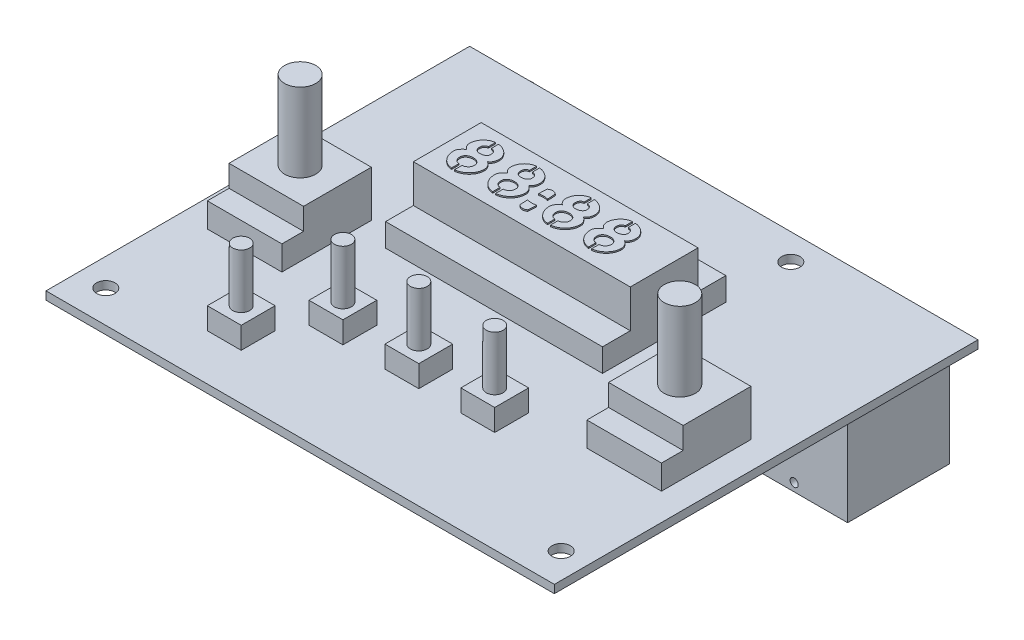
SolidWorks part; units mm, degrees
ref_plane "Front Plane" through (0, 0, 0) normal (0, 0, 1) x (1, 0, 0)
ref_plane "Top Plane" through (0, 0, 0) normal (0, 1, 0) x (1, 0, 0)
ref_plane "Right Plane" through (0, 0, 0) normal (1, 0, 0) x (0, 0, -1)
sketch "Sketch1" plane through (0, 0, 0) normal (0, 1, 0) x (1, 0, 0)
  line L1 (-47.625, 39.6875) -> (47.625, 39.6875)
  line L2 (-47.625, 39.6875) -> (-47.625, -39.6875)
  line L3 (-47.625, -39.6875) -> (47.625, -39.6875)
  line L4 (47.625, 39.6875) -> (47.625, -39.6875)
  line L5 (-47.625, 39.6875) -> (47.625, -39.6875) construction
  line L6 (-47.625, -39.6875) -> (47.625, 39.6875) construction
  point P0 (0, 0)
  dimension "D1" = 95.25
  dimension "D2" = 79.375
extrude "Boss-Extrude1" add sketch "Sketch1" along normal blind 1.524
hole_wizard "#29 (0.136) Diameter Hole1" positions "Sketch2" profile "Sketch3" hole size "#29" standard "ANSI Inch" end condition through all
sketch "Sketch2" plane through (0, 1.524, 0) normal (0, 1, 0) x (1, 0, 0)
  line L0 (47.625, -39.6875) -> (47.625, 39.6875) construction
  line L1 (-47.625, -39.6875) -> (47.625, -39.6875) construction
  line L2 (-47.625, 39.6875) -> (-47.625, -39.6875) construction
  line L3 (47.625, 39.6875) -> (-47.625, 39.6875) construction
  point P0 (42.8498, -33.6423)
  point P2 (17.4498, 34.7853)
  point P4 (-25.8318, 22.2123)
  point P6 (-42.4688, -33.6423)
  dimension "D1" = 4.7752
  dimension "D2" = 6.0452
  dimension "D3" = 6.0452
  dimension "D4" = 5.1562
  dimension "D5" = 30.1752
  dimension "D6" = 4.9022
  dimension "D7" = 17.4752
  dimension "D8" = 21.7932
sketch "Sketch3" plane through (42.8498, 1.524, 33.6423) normal (1, 0, 0) x (0, 0, 1)
  line L0 (0, 0) -> (0, 1.524)
  line L1 (0, 1.524) -> (1.7272, 1.524)
  line L2 (1.7272, 1.524) -> (1.7272, 0)
  line L5 (1.7272, 0) -> (0, 0)
  line L11 (0, -6.35) -> (0, 107.95) construction
  dimension "Thru Hole Dia." = 3.4544
  dimension "Thru Hole Depth" = 1.524
sketch "Sketch4" plane through (0, 1.524, 0) normal (0, 1, 0) x (1, 0, 0)
  line L0 (47.625, -39.6875) -> (47.625, 39.6875) construction
  line L1 (28.575, 2.2225) -> (42.545, 2.2225)
  line L2 (28.575, 2.2225) -> (28.575, -14.5415)
  line L3 (28.575, -14.5415) -> (42.545, -14.5415)
  line L4 (42.545, 2.2225) -> (42.545, -14.5415)
  line L5 (28.575, 2.2225) -> (42.545, -14.5415) construction
  line L6 (28.575, -14.5415) -> (42.545, 2.2225) construction
  line L7 (-47.625, -39.6875) -> (47.625, -39.6875) construction
  line L9 (-28.575, 2.2225) -> (-42.545, 2.2225)
  line L10 (-28.575, 2.2225) -> (-28.575, -14.5415)
  line L11 (-28.575, -14.5415) -> (-42.545, -14.5415)
  line L12 (-42.545, 2.2225) -> (-42.545, -14.5415)
  line L13 (-28.575, 2.2225) -> (-42.545, -14.5415) construction
  line L14 (-28.575, -14.5415) -> (-42.545, 2.2225) construction
  line L15 (-47.625, 39.6875) -> (-47.625, -39.6875) construction
  point P0 (35.56, -6.1595)
  point P9 (-35.56, -6.1595)
  dimension "D1" = 16.764
  dimension "D2" = 13.97
  dimension "D3" = 19.05
  dimension "D4" = 41.91
  dimension "D5" = 41.91
  dimension "D6" = 19.05
extrude "Boss-Extrude2" add sketch "Sketch4" along normal blind 4.572
sketch "Sketch5" plane through (0, 6.096, 0) normal (0, 1, 0) x (1, 0, 0)
  line L0 (-28.575, -14.5415) -> (-28.575, 2.2225) construction
  line L1 (-42.545, 2.2225) -> (-28.575, 2.2225)
  line L2 (-42.545, 2.2225) -> (-42.545, -10.4775)
  line L3 (-42.545, -10.4775) -> (-28.575, -10.4775)
  line L4 (-28.575, 2.2225) -> (-28.575, -10.4775)
  line L5 (42.545, -14.5415) -> (42.545, 2.2225) construction
  line L6 (28.575, 2.2225) -> (42.545, 2.2225)
  line L7 (28.575, 2.2225) -> (28.575, -10.4775)
  line L8 (28.575, -10.4775) -> (42.545, -10.4775)
  line L9 (42.545, 2.2225) -> (42.545, -10.4775)
  line L10 (0, 39.6875) -> (0, -39.6875) construction
  line L11 (47.625, 39.6875) -> (-47.625, 39.6875) construction
  line L12 (-47.625, -39.6875) -> (47.625, -39.6875) construction
  line L33 (-42.545, 2.2225) -> (-42.545, -14.5415) construction
  dimension "D1" = 12.7
extrude "Boss-Extrude3" add sketch "Sketch5" along normal blind 4.064
sketch "Sketch8" plane through (0, 1.524, 0) normal (0, 1, 0) x (1, 0, 0)
  line L0 (0, 39.6875) -> (0, -39.6875) construction
  line L1 (47.625, 39.6875) -> (-47.625, 39.6875) construction
  line L2 (-47.625, -39.6875) -> (47.625, -39.6875) construction
  line L3 (-47.625, 39.6875) -> (-47.625, -39.6875) construction
  line L5 (-26.035, -31.0515) -> (-19.685, -31.0515)
  line L6 (-26.035, -31.0515) -> (-26.035, -24.7015)
  line L7 (-26.035, -24.7015) -> (-19.685, -24.7015)
  line L8 (-3.175, -14.2875) -> (3.175, -20.6375) construction
  line L9 (-3.175, -20.6375) -> (3.175, -14.2875) construction
  line L10 (17.399, -14.2875) -> (17.399, -20.6375)
  line L11 (11.049, -14.2875) -> (17.399, -14.2875)
  line L12 (11.049, -14.2875) -> (11.049, -20.6375)
  line L13 (11.049, -20.6375) -> (17.399, -20.6375)
  line L14 (3.175, -14.2875) -> (3.175, -20.6375)
  line L15 (-3.175, -14.2875) -> (3.175, -14.2875)
  line L16 (-3.175, -14.2875) -> (-3.175, -20.6375)
  line L17 (-3.175, -20.6375) -> (3.175, -20.6375)
  line L18 (-11.049, -14.2875) -> (-11.049, -20.6375)
  line L19 (-17.399, -14.2875) -> (-11.049, -14.2875)
  line L20 (-17.399, -14.2875) -> (-17.399, -20.6375)
  line L21 (-17.399, -20.6375) -> (-11.049, -20.6375)
  line L22 (-19.685, -31.0515) -> (-19.685, -24.7015)
  line L23 (-26.035, -31.0515) -> (-19.685, -24.7015) construction
  line L24 (-26.035, -24.7015) -> (-19.685, -31.0515) construction
  point P6 (0, -17.4625)
  point P13 (-22.86, -27.8765)
  dimension "D1" = 30.226
  dimension "D2" = 58.674
  dimension "D3" = 6.35
  dimension "D4" = 53.975
  dimension "D5" = 27.94
  dimension "D6" = 14.986
extrude "Boss-Extrude5" add sketch "Sketch8" along normal blind 4.064
sketch "Sketch9" plane through (0, 5.588, 0) normal (0, 1, 0) x (1, 0, 0)
  line L0 (-17.399, -14.2875) -> (-11.049, -20.6375) construction
  line L1 (-3.175, -14.2875) -> (3.175, -20.6375) construction
  line L2 (11.049, -14.2875) -> (17.399, -20.6375) construction
  line L3 (-26.035, -24.7015) -> (-19.685, -31.0515) construction
  circle A0 centre (-13.9422, -17.7443) radius 1.5875
  circle A1 centre (0, -17.4625) radius 1.5875
  circle A2 centre (14.224, -17.4625) radius 1.5875
  circle A3 centre (-22.86, -27.8765) radius 1.5875
  dimension "D1" = 3.175
extrude "Boss-Extrude6" add sketch "Sketch9" along normal blind 10.16
sketch "Sketch10" plane through (0, 10.16, 0) normal (0, 1, 0) x (1, 0, 0)
  line L0 (-42.545, 2.2225) -> (-28.575, -10.4775) construction
  line L1 (28.575, 2.2225) -> (42.545, -10.4775) construction
  circle A0 centre (-35.56, -4.1275) radius 2.921
  circle A1 centre (35.56, -4.1275) radius 2.921
  dimension "D1" = 5.842
extrude "Boss-Extrude7" add sketch "Sketch10" along normal blind 14.732
sketch "Sketch11" plane through (0, 0, -39.6875) normal (0, 0, -1) x (-1, 0, 0)
  line L0 (-47.625, 0) -> (47.625, 0) construction
  line L1 (-42.2402, 0) -> (-22.225, 0)
  line L2 (-42.2402, 0) -> (-42.2402, -21.336)
  line L3 (-42.2402, -21.336) -> (-22.225, -21.336)
  line L4 (-22.225, 0) -> (-22.225, -21.336)
  line L5 (-47.625, 1.524) -> (-47.625, 0) construction
  dimension "D1" = 25.4
  dimension "D2" = 20.0152
  dimension "D3" = 21.336
extrude "Boss-Extrude8" add sketch "Sketch11" against normal blind 19.05 separate body
sketch "Sketch12" plane through (0, 0, -39.6875) normal (0, 0, -1) x (-1, 0, 0)
  line L0 (-32.2326, 0) -> (-32.2326, -21.336) construction
  line L1 (-22.225, 0) -> (-42.2402, 0) construction
  line L2 (-42.2402, -21.336) -> (-22.225, -21.336) construction
  circle A0 centre (-32.2326, -10.541) radius 6.985
  dimension "D1" = 13.97
  dimension "D2" = 10.795
extrude "Cut-Extrude1" cut sketch "Sketch12" against normal blind 3.175
hole_wizard "#53 (0.0595) Diameter Hole1" positions "Sketch13" profile "Sketch14" hole size "#53" standard "ANSI Inch" end condition through all
sketch "Sketch13" plane through (0, 0, -39.6875) normal (0, 0, -1) x (-1, 0, 0)
  line L1 (-32.2326, -10.541) -> (-32.2326, -21.336) construction
  line L2 (-42.2402, -21.336) -> (-22.225, -21.336) construction
  line L3 (-23.4886, -5.4927) -> (-32.2326, -10.541) construction
  line L5 (-40.9765, -5.4927) -> (-32.2326, -10.541) construction
  line L7 (-22.225, -21.336) -> (-22.225, 0) construction
  line L8 (-42.2402, 0) -> (-42.2402, -21.336) construction
  point P0 (-40.9765, -5.4927)
  point P2 (-23.4886, -5.4927)
  point P14 (-32.2326, -19.8183)
  dimension "D1" = 1.5176
  dimension "D2" = 120
  dimension "D3" = 120
  dimension "D4" = 1.2637
  dimension "D5" = 1.2637
sketch "Sketch14" plane through (40.9765, -5.4927, -39.6875) normal (1, 0, 0) x (0, 1, 0)
  line L0 (0, 0) -> (0, 79.375)
  line L1 (0, 79.375) -> (0.7556, 79.375)
  line L2 (0.7556, 79.375) -> (0.7556, 0)
  line L5 (0.7556, 0) -> (0, 0)
  line L11 (0, -6.35) -> (0, 107.95) construction
  dimension "Thru Hole Dia." = 1.5113
  dimension "Thru Hole Depth" = 79.375
sketch "Sketch15" plane through (0, 0, -39.6875) normal (0, 0, -1) x (-1, 0, 0)
  line L0 (-47.625, 0) -> (47.625, 0) construction
  line L1 (34.925, 0) -> (40.894, 0)
  line L2 (34.925, 0) -> (34.925, -5.334)
  line L3 (34.925, -5.334) -> (40.894, -5.334)
  line L4 (40.894, 0) -> (40.894, -5.334)
  line L5 (47.625, 1.524) -> (47.625, 0) construction
  dimension "D1" = 5.969
  dimension "D2" = 5.334
  dimension "D3" = 12.7
extrude "Boss-Extrude9" add sketch "Sketch15" against normal blind 13.97
sketch "Sketch16" plane through (0, 0, -39.6875) normal (0, 0, -1) x (-1, 0, 0)
  line L0 (34.925, 0) -> (40.894, -5.334) construction
  circle A0 centre (37.9095, -2.667) radius 1.778
  circle A1 centre (37.9095, -2.667) radius 2.54
  dimension "D1" = 5.08
  dimension "D2" = 3.556
extrude "Boss-Extrude10" add sketch "Sketch16" along normal blind 2.032 draft 9
sketch "Sketch17" plane through (0, 0, -39.6875) normal (0, 0, -1) x (-1, 0, 0)
  circle A0 centre (37.9095, -2.667) radius 1.778
extrude "Cut-Extrude2" cut sketch "Sketch17" against normal blind 12.7
sketch "Sketch18" plane through (0, 1.524, 0) normal (0, 1, 0) x (1, 0, 0)
  line L0 (-47.625, 39.6875) -> (-47.625, -39.6875) construction
  line L1 (-22.733, -0.9525) -> (17.907, -0.9525)
  line L2 (-22.733, -0.9525) -> (-22.733, 22.1615)
  line L3 (-22.733, 22.1615) -> (17.907, 22.1615)
  line L4 (17.907, -0.9525) -> (17.907, 22.1615)
  line L5 (47.625, 39.6875) -> (-47.625, 39.6875) construction
  dimension "D1" = 40.64
  dimension "D2" = 23.114
  dimension "D3" = 65.532
  dimension "D4" = 40.64
extrude "Boss-Extrude11" add sketch "Sketch18" along normal blind 4.318
sketch "Sketch19" plane through (0, 5.842, 0) normal (0, 1, 0) x (1, 0, 0)
  line L0 (-22.733, 22.1615) -> (17.907, -0.9525) construction
  line L1 (17.907, -0.9525) -> (17.907, 22.1615) construction
  line L2 (-22.733, 4.2545) -> (17.907, 4.2545)
  line L3 (-22.733, 4.2545) -> (-22.733, 16.9545)
  line L4 (-22.733, 16.9545) -> (17.907, 16.9545)
  line L5 (17.907, 4.2545) -> (17.907, 16.9545)
  line L6 (-22.733, 4.2545) -> (17.907, 16.9545) construction
  line L7 (-22.733, 16.9545) -> (17.907, 4.2545) construction
  point P4 (-2.413, 10.6045)
  dimension "D1" = 12.7
extrude "Boss-Extrude12" add sketch "Sketch19" along normal blind 7.112
sketch "Sketch20" plane through (0, 0, 0) normal (0, -1, 0) x (1, 0, 0)
  line L0 (-47.625, 39.6875) -> (47.625, 39.6875) construction
  line L1 (17.653, 35.8775) -> (-15.367, 35.8775)
  line L2 (17.653, 35.8775) -> (17.653, 33.4675)
  line L3 (17.653, 33.4675) -> (-15.367, 33.4675)
  line L4 (-15.367, 35.8775) -> (-15.367, 33.4675)
  line L5 (47.625, 39.6875) -> (47.625, -39.6875) construction
  dimension "D1" = 33.02
  dimension "D2" = 2.41
  dimension "D3" = 3.81
  dimension "D4" = 29.972
extrude "Boss-Extrude13" add sketch "Sketch20" along normal blind 2.54
sketch "Sketch21" plane through (0, 0, 0) normal (0, -1, 0) x (1, 0, 0)
  line L0 (47.625, -39.6875) -> (-34.925, -39.6875) construction
  line L1 (3.429, -39.6875) -> (-5.461, -39.6875)
  line L2 (3.429, -39.6875) -> (3.429, -35.1155)
  line L3 (3.429, -35.1155) -> (-5.461, -35.1155)
  line L4 (-5.461, -39.6875) -> (-5.461, -35.1155)
  line L5 (47.625, 39.6875) -> (47.625, -39.6875) construction
  dimension "D1" = 8.89
  dimension "D2" = 4.572
  dimension "D3" = 53.086
extrude "Boss-Extrude14" add sketch "Sketch21" along normal blind 4.826
sketch "Sketch22" plane through (0, 0, -39.6875) normal (0, 0, -1) x (-1, 0, 0)
  line L0 (-3.429, 0) -> (5.461, -4.826) construction
  line L1 (5.461, -4.826) -> (5.461, 0) construction
  line L2 (-3.429, -3.429) -> (5.461, -3.429)
  line L3 (-3.429, -3.429) -> (-3.429, -1.397)
  line L4 (-3.429, -1.397) -> (5.461, -1.397)
  line L5 (5.461, -3.429) -> (5.461, -1.397)
  line L6 (-3.429, -3.429) -> (5.461, -1.397) construction
  line L7 (-3.429, -1.397) -> (5.461, -3.429) construction
  point P4 (1.016, -2.413)
  dimension "D1" = 2.032
extrude "Boss-Extrude15" add sketch "Sketch22" along normal blind 1.524
sketch "Sketch23" plane through (0, 12.954, 0) normal (0, 1, 0) x (1, 0, 0)
  line L0 (17.907, 4.2545) -> (17.907, 16.9545) construction
  line L1 (17.907, 16.9545) -> (-22.733, 16.9545) construction
  text T0 "88:88" font "Stencilia-Bold" height in points 25
  dimension "D1" = 39.3082
  dimension "D2" = 10.3887
extrude "Boss-Extrude16" add sketch "Sketch23" along normal blind 0.254
